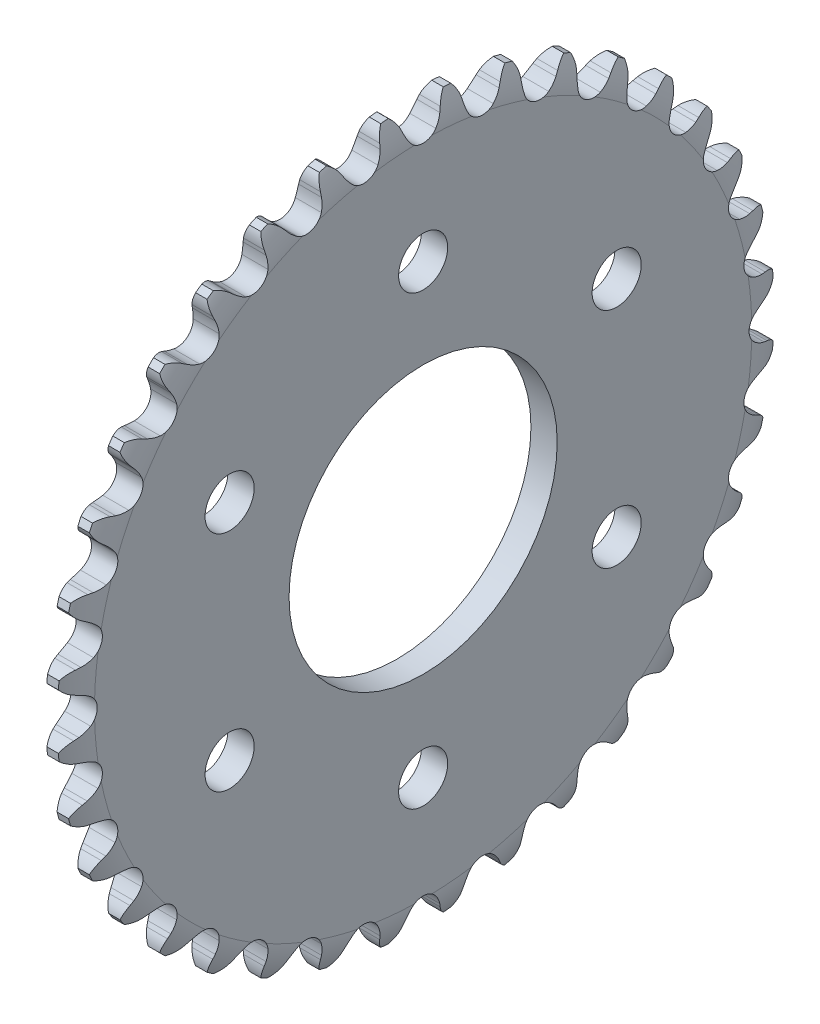
SolidWorks part; units mm, degrees
material "6061-T6 (SS)"
ref_plane "Plane1" through (0, 0, 0) normal (0, 0, 1) x (1, 0, 0)
ref_plane "Plane2" through (0, 0, 0) normal (0, 1, 0) x (1, 0, 0)
ref_plane "Plane3" through (0, 0, 0) normal (1, 0, 0) x (0, 0, -1)
sketch "Clipboard" plane through (0, 0, 0) normal (0, 1, 0) x (1, 0, 0)
  line L0 (0, 0) -> (5.1373, -3.7324)
  line L1 (-15, 0) -> (100, 0) construction
  line L2 (0, 0) -> (-0.5218, 0.5897)
  line L3 (0, 0) -> (-2.9658, 1.1335)
  line L4 (0, 0) -> (2.5686, 1.8662)
  line L5 (0, 0) -> (-47.5972, -17.7524)
  line L6 (0, 0) -> (-2.3214, -1.5662)
  line L7 (-0.5218, 0.5897) -> (40.049, 31.1619)
  line L8 (-76.2, 38.1) -> (-51.7144, 38.1)
  line L9 (-73.2057, 38.5609) -> (-73.0533, 38.5634)
  line L10 (-73.0533, 76.1892) -> (-66.6525, 76.1892)
  circle A0 centre (0, 0) radius 1.651
  circle A1 centre (0, 0) radius 32.7344
  circle A2 centre (0, 0) radius 38.1
  dimension "Dr" = 3.302
  dimension "MHD" = 65.4688
  dimension "Hub_dia" = 76.2
  dimension "Num_teeth" = 36
  dimension "Pitch" = 6.35
  dimension "Width" = 3.175
  dimension "Chamfer_wid" = 0.7874
  dimension "Chamfer_dep" = 3.175
  dimension "Overall_len" = 50.8
  dimension "Show_teeth" = 36
  dimension "Thickness" = 2.8004
  dimension "OAL" = 50.8001
  dimension "T_dim" = 24.4856
  dimension "Width_const" = 0.1524
  dimension "Width_factor" = 0.93
  dimension "Num_strands" = 1
  dimension "Transv_pitch" = 6.4008
sketch "BasProSke" plane through (0, 0, 0) normal (0, 1, 0) x (1, 0, 0)
  line L0 (-10, 0) -> (60, 0) construction
  line L1 (0, 0) -> (0, 35.0204)
  line L2 (0, 0) -> (2.8003, 0)
  line L3 (2.8003, 0) -> (2.8003, 35.0204)
  line L4 (2.0129, 38.1954) -> (0.7874, 38.1954)
  arc A0 (0, 35.0204) -> (0.7874, 38.1954) centre (6.7949, 35.0204) cw
  arc A1 (2.8003, 35.0204) -> (2.0129, 38.1954) centre (-3.9946, 35.0204) ccw
  dimension "D1" = 6.7949
  dimension "G1" = 0.7874
  dimension "G2" = 0.7874
  dimension "H2" = 3.175
  dimension "Diameter" = 76.3908
  dimension "H1" = 3.175
  dimension "Thickness" = 2.8004
revolve "Base-Revolve" add sketch "BasProSke" angle 360 about L0
sketch "GrvSke" plane through (0, 0, 0) normal (0, 1, 0) x (1, 0, 0)
  line L0 (2.8004, 35.0204) -> (2.8003, 32.7344)
  line L1 (2.8003, 32.7344) -> (6.4008, 32.7344)
  line L2 (6.4008, 32.7344) -> (6.4008, 35.0204)
  line L3 (2.0129, 38.1954) -> (7.1882, 38.1954)
  line L4 (4.6006, 0) -> (4.6006, 52.07) construction
  line L5 (-10, 0) -> (60, 0) construction
  line L6 (0, 0) -> (35.56, 0) construction
  arc A0 (6.4008, 35.0204) -> (7.1882, 38.1954) centre (13.1957, 35.0204) cw
  arc A1 (2.8004, 35.0204) -> (2.0129, 38.1954) centre (-3.9946, 35.0204) ccw
  dimension "Diameter" = 76.3908
  dimension "H1" = 3.175
  dimension "Grv_diam" = 65.4688
  dimension "Grv_width" = 3.6004
  dimension "Offset" = 4.6006
  dimension "G1" = 0.7874
revolve "Groove" [suppressed] cut sketch "GrvSke" angle 360 about L6
pattern_linear "Grooves" [suppressed]
sketch "TooCutSke" plane through (0, 0, 0) normal (1, 0, 0) x (0, 0, -1)
  line L0 (1.9526, 36.5067) -> (2.1137, 36.9439)
  line L1 (0, 0) -> (0, 107) construction
  line L2 (0, 36.429) -> (-10, 36.429) construction
  line L3 (-1.9526, 36.5067) -> (-2.1137, 36.9439)
  arc A0 (1.3615, 35.4154) -> (1.9526, 36.5067) centre (-2.1189, 38.0065) ccw
  arc A1 (1.3615, 35.4154) -> (-1.3615, 35.4154) centre (0, 36.429) cw
  arc A2 (2.1137, 36.9439) -> (4.6052, 38.6813) centre (4.6052, 36.0261) cw
  arc A3 (-1.3615, 35.4154) -> (-1.9526, 36.5067) centre (2.1189, 38.0065) cw
  arc A4 (-2.1137, 36.9439) -> (-4.6052, 38.6813) centre (-4.6052, 36.0261) ccw
  arc A5 (4.6052, 38.6813) -> (-4.6052, 38.6813) centre (0, 0) ccw
  dimension "R" = 1.6974
  dimension "E" = 4.339
  dimension "F" = 2.6552
  dimension "Pitch_radius" = 36.429
  dimension "W" = 4.6052
  dimension "V" = 0.4029
  dimension "A" = 36.667
  dimension "B" = 16.444
extrude "ToothCut" cut sketch "TooCutSke" along normal through all
pattern_circular "TeethCuts" count 36 every 10 about axis through (-10, 0, 0) along (1, 0, 0) of "ToothCut"
sketch "HubNeaOneSke" plane through (0, 0, 0) normal (-1, 0, 0) x (0, 0, 1)
  circle A0 centre (0, 0) radius 32.7344
  dimension "Diameter" = 65.4688
extrude "HubNearOne" [suppressed] add sketch "HubNeaOneSke" along normal blind 47.9997
sketch "HubNeaBotSke" plane through (0, 0, 0) normal (-1, 0, 0) x (0, 0, 1)
  circle A0 centre (0, 0) radius 32.7344
  dimension "Diameter" = 65.4688
extrude "HubNearBoth" [suppressed] add sketch "HubNeaBotSke" along normal blind 23.9999
ref_plane "FarPln" through (2.8004, 0, 0) normal (1, 0, 0) x (0, 0, -1)
sketch "HubFarSke" plane through (2.8004, 0, 0) normal (1, 0, 0) x (0, 0, -1)
  circle A0 centre (0, 0) radius 32.7344
  dimension "Diameter" = 65.4688
extrude "HubFar" [suppressed] add sketch "HubFarSke" along normal blind 23.9999
sketch "BorSke" plane through (0, 0, 0) normal (1, 0, 0) x (0, 0, -1)
  circle A0 centre (0, 0) radius 11.1125
  dimension "Diameter" = 22.225
extrude "Bore" cut sketch "BorSke" along normal mid plane 101.6001
sketch "KeySke" plane through (0, 0, 0) normal (1, 0, 0) x (0, 0, -1)
  line L0 (-2.3813, 0) -> (-2.3813, 13.3731)
  line L1 (-2.3813, 13.3731) -> (2.3813, 13.3731)
  line L2 (2.3813, 13.3731) -> (2.3813, 0)
  line L3 (0, 0) -> (0, 34) construction
  line L4 (-2.3813, 0) -> (2.3813, 0)
  dimension "Offset" = 13.3731
  dimension "Width" = 4.7625
extrude "Keyway" [suppressed] cut sketch "KeySke" along normal mid plane 101.6001
pattern_circular "Keyway2" [suppressed] count 2 every 90 about axis through (-10, 0, 0) along (1, 0, 0)
sketch "Sketch1" plane through (2.8003, 0, 0) normal (1, 0, 0) x (0, 0, -1)
  arc A0 (-2.6122, 23.6688) -> (2.6122, 23.6688) centre (0, 0) ccw
  circle A1 centre (0, 23.8125) radius 2.6162
  dimension "D1" = 47.625
  dimension "D2" = 5.2324
extrude "Extrude1" cut sketch "Sketch1" against normal through all contours A1 region at (2.8003, 23.8125, 0)
pattern_circular "CirPattern1" count 6 over 360 about axis through (2.8003, 0, 0) along (1, 0, 0) of "Extrude1"
sketch "Sketch2" plane through (2.8003, 0, 0) normal (1, 0, 0) x (0, 0, -1)
  circle A0 centre (0, 0) radius 14.2875
  dimension "D1" = 28.575
extrude "Extrude2" cut sketch "Sketch2" against normal through all
equation "\"Num_teeth@Clipboard\" = int( \"Num_teeth@Clipboard\" )"
equation "\"Num_teeth@Clipboard\" = ((sgn( \"Num_teeth@Clipboard\" - 5.0)+1)*( \"Num_teeth@Clipboard\" - 5.0))/2 +5.0"
equation "\"Num_teeth@Clipboard\" = ((sgn( \"Num_teeth@Clipboard\" - 200.0)-1)*( \"Num_teeth@Clipboard\" - 200.0))/-2 +200.0"
equation "\"MHD@Clipboard\" = \"Pitch@Clipboard\" * (1.0 / tan(3.14159265 / \"Num_teeth@Clipboard\" ) - 1.0) - 0.03"
equation "\"Thickness@Clipboard\"  = \"Width@Clipboard\" * \"Width_factor@Clipboard\" - \"Width_const@Clipboard\" + (\"Num_strands@Clipboard\" - 1) * \"Transv_pitch@Clipboard\""
equation "\"OAL@Clipboard\" = \"Thickness@Clipboard\""
equation "\"MHD@Clipboard\" = ((sgn( \"MHD@Clipboard\" - \"Hub_dia@Clipboard\" )-1)*( \"MHD@Clipboard\" - \"Hub_dia@Clipboard\" ))/-2+ \"Hub_dia@Clipboard\""
equation "\"OAL@Clipboard\" = ((sgn( \"OAL@Clipboard\" - \"Overall_len@Clipboard\" )+1)*( \"OAL@Clipboard\" - \"Overall_len@Clipboard\" ))/2 + \"Overall_len@Clipboard\" + 0.000002"
equation "\"Num_teeth@TeethCuts\" = int( \"Show_teeth@Clipboard\" ) + 1"
equation "\"Num_teeth@TeethCuts\" = ((sgn( \"Num_teeth@TeethCuts\" - \"Num_teeth@Clipboard\" )-1)*( \"Num_teeth@TeethCuts\" - \"Num_teeth@Clipboard\" ))/-2+ \"Num_teeth@Clipboard\""
equation "\"Num_teeth@TeethCuts\" = ((sgn( \"Num_teeth@TeethCuts\" - 2.0)+1)*( \"Num_teeth@TeethCuts\" - 2.0))/2 +2.0"
equation "\"Angle@TeethCuts\" = 360.0 / \"Num_teeth@Clipboard\""
equation "\"Pitch_radius@TooCutSke\" = ( \"Pitch@Clipboard\" / 2.0) / sin(3.14159265 / \"Num_teeth@Clipboard\" )  'ma"
equation "\"R@TooCutSke\"  = \"Dr@Clipboard\" * 0.5025 + 0.0015"
equation "\"A@TooCutSke\" = 35.0 + (60.0 / \"Num_teeth@Clipboard\")"
equation "\"E@TooCutSke\"  = \"Dr@Clipboard\" * 1.3025 + 0.0015"
equation "\"B@TooCutSke\"  = 18.0 - (56.0 / \"Num_teeth@Clipboard\" )"
equation "\"W@TooCutSke\" = 1.4 * \"Dr@Clipboard\" * cos(3.14159265 / \"Num_teeth@Clipboard\" )"
equation "\"V@TooCutSke\" = 1.4 * \"Dr@Clipboard\" * sin(3.14159265 / \"Num_teeth@Clipboard\" )"
equation "\"Diameter@BasProSke\" = 2.0 * ( (0.3 * \"Pitch@Clipboard\" ) +  \"Pitch@Clipboard\" / 2.0 / tan(3.14159265 / \"Num_teeth@Clipboard\" ))"
equation "\"Thickness@BasProSke\"  = \"Thickness@Clipboard\""
equation "\"G1@BasProSke\" =  \"Chamfer_wid@Clipboard\""
equation "\"G2@BasProSke\" =  \"Chamfer_wid@Clipboard\""
equation "\"H1@BasProSke\" =  \"Chamfer_dep@Clipboard\""
equation "\"H2@BasProSke\" =  \"Chamfer_dep@Clipboard\""
equation "\"Diameter@GrvSke\" = \"Diameter@BasProSke\""
equation "\"G1@GrvSke\" = \"Chamfer_wid@Clipboard\""
equation "\"H1@GrvSke\" = \"Chamfer_dep@Clipboard\""
equation "\"Grv_diam@GrvSke\" =  \"Pitch@Clipboard\" * (1.0 / tan(3.14159265 / \"Num_teeth@Clipboard\" ) - 1.0) - 0.03"
equation "\"Grv_width@GrvSke\" =  \"Transv_pitch@Clipboard\" - ( \"Width@Clipboard\" * \"Width_factor@Clipboard\" - \"Width_const@Clipboard\" )"
equation "\"Offset@GrvSke\" = \"Grv_width@GrvSke\" / 2.0 + ( \"Width@Clipboard\" * \"Width_factor@Clipboard\" - \"Width_const@Clipboard\" )"
equation "\"Offset@Grooves\" = \"Transv_pitch@Clipboard\""
equation "\"Num_grvs@Grooves\" = \"Num_strands@Clipboard\""
equation "\"Num_grvs@Grooves\" = \"Num_grvs@Grooves\" - 1 * sgn( \"Num_grvs@Grooves\" -1)"
equation "\"Diameter@HubNeaOneSke\" = \"MHD@Clipboard\""
equation "\"Length@HubNearOne\" = \"OAL@Clipboard\" - \"Thickness@BasProSke\""
equation "\"Diameter@HubNeaBotSke\" = \"MHD@Clipboard\""
equation "\"Length@HubNearBoth\" = ( \"OAL@Clipboard\" - \"Thickness@BasProSke\" ) / 2.0"
equation "\"Thickness@FarPln\" = \"Thickness@BasProSke\""
equation "\"Diameter@HubFarSke\" = \"MHD@Clipboard\""
equation "\"Length@HubFar\" = ( \"OAL@Clipboard\" - \"Thickness@BasProSke\" ) / 2.0"
equation "\"D1@Bore\" = \"OAL@Clipboard\" * 2.0"
equation "\"D1@Keyway\" = \"OAL@Clipboard\" * 2.0"
equation "\"Offset@KeySke\" = \"T_dim@Clipboard\" - \"Diameter@BorSke\" / 2.0"
